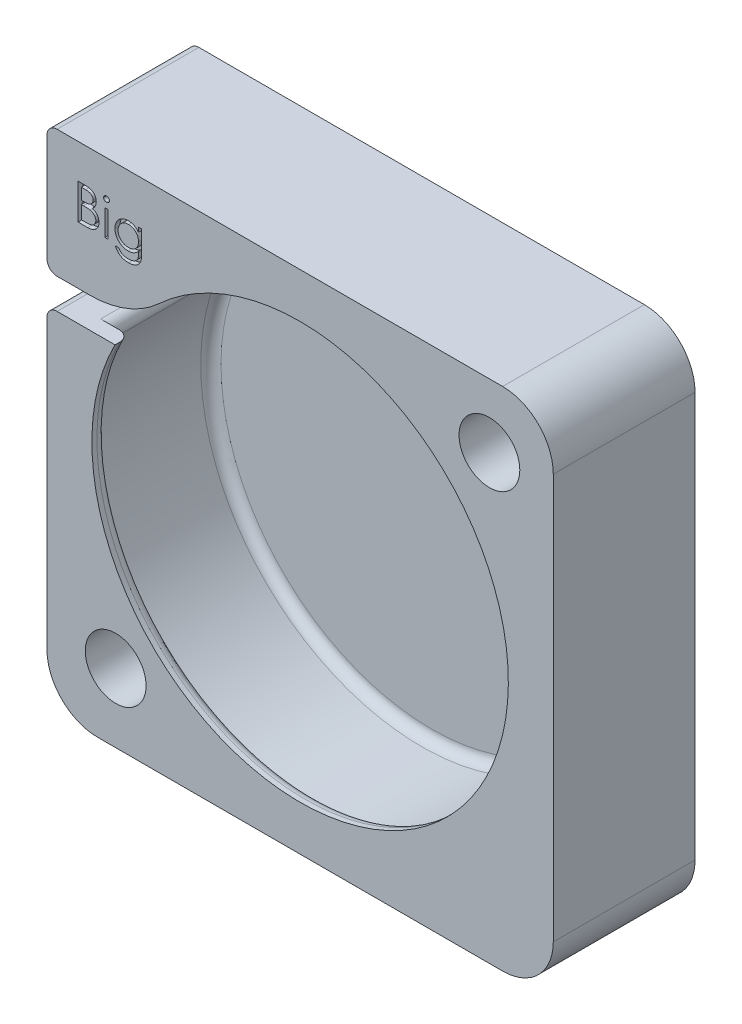
SolidWorks part; units mm, degrees
material "Plastique personnalisé"
ref_plane "Plan de face" through (0, 0, 0) normal (0, 0, 1) x (1, 0, 0)
ref_plane "Plan de dessus" through (0, 0, 0) normal (0, 1, 0) x (1, 0, 0)
ref_plane "Plan de droite" through (0, 0, 0) normal (1, 0, 0) x (0, 0, -1)
sketch "Esquisse4" plane through (0, 0, 0) normal (0, 0, 1) x (1, 0, 0)
  line L1 (0, 0) -> (45, 0)
  line L2 (0, 0) -> (0, -45)
  line L3 (5, -50) -> (45, -50)
  line L4 (50, -5) -> (50, -45)
  arc A0 (0, -45) -> (5, -50) centre (5, -45) ccw
  arc A1 (45, 0) -> (50, -5) centre (45, -5) cw
  arc A2 (45, -50) -> (50, -45) centre (45, -45) ccw
  point P9 (50, 0)
  point P12 (50, -50)
  dimension "D3" = 5
  dimension "D1" = 50
  dimension "D2" = 50
extrude "Boss.-Extru.2" add sketch "Esquisse4" along normal blind 14
sketch "Esquisse5" plane through (0, 0, 14) normal (0, 0, 1) x (1, 0, 0)
  line L0 (50, -25) -> (0, -25) construction
  line L1 (50, -45) -> (50, -5) construction
  line L2 (0, 0) -> (0, -45) construction
  circle A0 centre (25, -25) radius 13.5
  dimension "D1" = 27
extrude "Enlèv. mat.-Extru.1" cut sketch "Esquisse5" against normal blind 13
sketch "Esquisse6" plane through (0, 0, 14) normal (0, 0, 1) x (1, 0, 0)
  line L0 (19.714, -12.5779) -> (0, -12.5779)
  line L1 (0, 0) -> (0, -45) construction
  line L2 (0, -12.5779) -> (0, -15.5779)
  line L3 (0, -15.5779) -> (19.714, -15.5779)
  line L4 (19.714, -15.5779) -> (19.714, -12.5779)
  circle A0 centre (25, -25) radius 13.5 construction
  circle A1 centre (25, -25) radius 13.5 construction
  dimension "D1" = 3
extrude "Enlèv. mat.-Extru.2" cut sketch "Esquisse6" against normal blind 13 and the other way blind 1.5
sketch "Esquisse7" plane through (0, 0, 14) normal (0, 0, 1) x (1, 0, 0)
  line L0 (48.5355, -1.4645) -> (1.4645, -48.5355) construction
  arc A0 (50, -5) -> (45, 0) centre (45, -5) ccw construction
  arc A1 (0, -45) -> (5, -50) centre (5, -45) ccw construction
sketch "Esquisse8" plane through (0, 0, 14) normal (0, 0, 1) x (1, 0, 0)
  line L0 (48.5355, -1.4645) -> (34.5459, -15.4541) construction
  line L1 (48.5355, -1.4645) -> (1.4645, -48.5355) construction
  line L2 (1.4645, -48.5355) -> (15.4541, -34.5459) construction
  arc A0 (15.3318, -15.5779) -> (19.714, -12.5779) centre (25, -25) ccw construction
  arc A1 (15.3318, -15.5779) -> (19.714, -12.5779) centre (25, -25) ccw construction
sketch "Esquisse9" plane through (0, 0, 14) normal (0, 0, 1) x (1, 0, 0)
  line L0 (48.5355, -1.4645) -> (36.5352, -13.4648) construction
  line L1 (48.5355, -1.4645) -> (1.4645, -48.5355) construction
  line L2 (36.5352, -13.4648) -> (26.3702, -3.2999) construction
  line L3 (1.4645, -48.5355) -> (13.4607, -36.5393) construction
  line L4 (13.4607, -36.5393) -> (3.1117, -26.1903) construction
  arc A1 (0, -45) -> (5, -50) centre (5, -45) ccw construction
  circle A3 centre (6.7861, -43.2139) radius 3
  circle A4 centre (43.6947, -6.3053) radius 3
extrude "Enlèv. mat.-Extru.3" cut sketch "Esquisse9" against normal through all
fillet "Congé1" radius 1 1 edges at (0, 0, 7)
fillet "Congé2" radius 1 1 edges at (0, -12.5779, 7.5)
fillet "Congé3" radius 1 1 edges at (0, -15.5779, 7.5)
fillet "Congé4" radius 1 1 edges at (15.3318, -15.5779, 7.5)
sketch "Esquisse10" plane through (0, 0, 14) normal (0, 0, 1) x (1, 0, 0)
  line L0 (48.5355, -1.4645) -> (1.4645, -48.5355) construction
  circle A0 centre (25, -25) radius 20.5636
extrude "Enlèv. mat.-Extru.4" cut sketch "Esquisse10" against normal up to surface (13 mm away) up to face at (9.3687, -17.4336, 1)
fillet "Congé5" radius 10 1 edges at (8.6124, -12.5779, 7.5)
ref_plane "Plan1" through (0, 0, 12.5) normal (0, 0, 1) x (1, 0, 0)
sketch "Esquisse11" plane through (0, 0, 12.5) normal (0, 0, 1) x (1, 0, 0)
  line L0 (48.5355, -1.4645) -> (1.4645, -48.5355) construction
  circle A0 centre (25, -25) radius 21.8118
extrude "Enlèv. mat.-Extru.6" cut sketch "Esquisse11" against normal up to surface (11.5 mm away) up to face at (8.0449, -17.1027, 1)
fillet "Congé6" radius 1 2 edges at (9.3513, -11.1672, 12.5) (41.3728, -37.4415, 12.5)
fillet "Congé7" radius 1 1 edges at (7.4527, -12.0445, 7.25)
fillet "Congé8" radius 1 1 edges at (5.3283, -15.5779, 6.75)
sketch "Esquisse12" plane through (0, 0, 14) normal (0, 0, 1) x (1, 0, 0)
  text T0 "Big"
extrude "Enlèv. mat.-Extru.7" cut sketch "Esquisse12" against normal blind 0.5
fillet "Congé9" radius 1 8 edges at (0.2929, -12.285, 1) (2.6151, -12.5779, 1) (5.6978, -12.4696, 1) (7.4141, -12.0113, 1) (0.2929, -15.8708, 1) (2.3999, -15.5779, 1) (4.6273, -16.0163, 1) (43.9913, -35.7278, 1)
